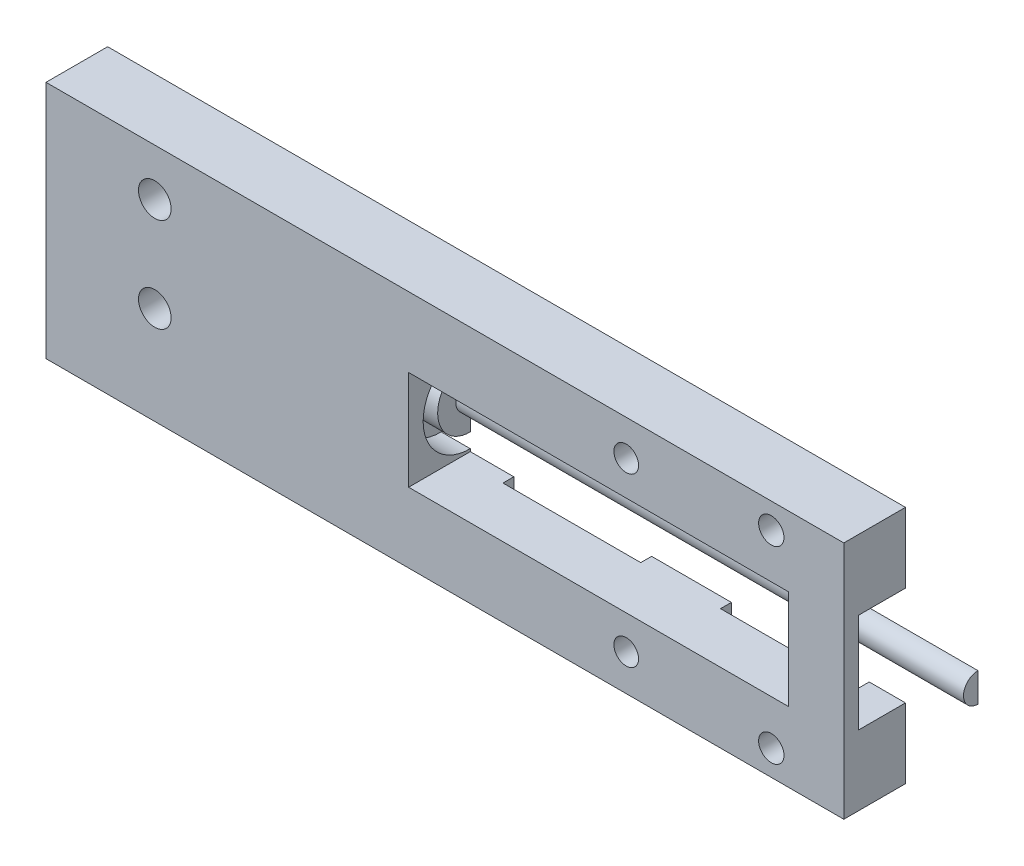
SolidWorks part; units mm, degrees
ref_plane "Plano frontal" through (0, 0, 0) normal (0, 0, 1) x (1, 0, 0)
ref_plane "Plano superior" through (0, 0, 0) normal (0, 1, 0) x (1, 0, 0)
ref_plane "Plano direito" through (0, 0, 0) normal (1, 0, 0) x (0, 0, -1)
sketch "Esboço4" plane through (0, 0, 0) normal (0, 0, 1) x (1, 0, 0)
  line L0 (-80, 16.5) -> (30, 16.5)
  line L1 (-80, -16.5) -> (-80, 16.5)
  line L2 (-80, -16.5) -> (30, -16.5)
  line L3 (30, 16.5) -> (30, 6.85)
  line L4 (30, -16.5) -> (30, -6.85)
  line L5 (30, -6.85) -> (-30, -6.85)
  line L6 (30, 6.85) -> (-30, 6.85)
  line L7 (-30, 6.85) -> (-30, -6.85)
extrude "Ressalto-extrusão1" add sketch "Esboço4" along normal blind 8.5
ref_plane "Plano1" through (-30, 6.85, 8.5) normal (0, 1, 0) x (1, 0, 0)
sketch "Esboço5" plane through (-30, 6.85, 8.5) normal (0, 1, 0) x (1, 0, 0)
  line L0 (6, 7) -> (25, 7)
  line L1 (55, 8.5) -> (55, 7)
  line L2 (6, 7) -> (6, 8.5)
  line L3 (6, 8.5) -> (25, 8.5)
  line L4 (0, 8.5) -> (60, 8.5) construction
  line L5 (25, 8.5) -> (25, 7)
  line L6 (36, 8.5) -> (36, 7)
  line L7 (36, 7) -> (55, 7)
  line L8 (36, 8.5) -> (55, 8.5)
ref_plane "Plano2" through (-30, -6.85, 8.5) normal (0, 1, 0) x (1, 0, 0)
sketch "Esboço8" plane through (-30, -6.85, 8.5) normal (0, 1, 0) x (1, 0, 0)
  line L0 (6, 7) -> (25, 7)
  line L1 (6, 7) -> (6, 8.5)
  line L2 (60, 8.5) -> (0, 8.5) construction
  line L3 (6, 8.5) -> (25, 8.5)
  line L4 (25, 8.5) -> (25, 7)
  line L5 (55, 8.5) -> (55, 7)
  line L6 (36, 8.5) -> (36, 7)
  line L7 (55, 7) -> (36, 7)
  line L8 (55, 8.5) -> (36, 8.5)
extrude "Corte-extrusão1" cut sketch "Esboço8" against normal blind 3 contours L0 L4 L3 L1
extrude "Corte-extrusão2" cut sketch "Esboço5" along normal blind 3
ref_plane "Plano4" through (-80, 16.5, 8.5) normal (0, 0, -1) x (-1, 0, 0)
sketch "Esboço9" plane through (-80, 16.5, 8.5) normal (0, 0, -1) x (-1, 0, 0)
  circle A0 centre (-15, -6.5) radius 3
  circle A1 centre (-15, -19.5) radius 3
  circle A2 centre (-42, -19.5) radius 3
  circle A3 centre (-42, -6.5) radius 3
  circle A4 centre (-42, -6.5) radius 1.62
  circle A5 centre (-42, -19.5) radius 1.62
sketch "Esboço11" plane through (0, 0, 8.5) normal (0, 0, 1) x (1, 0, 0)
  circle A0 centre (-65, 10) radius 2.25
  circle A1 centre (-65, 10) radius 3 construction
  circle A2 centre (0, 11.6) radius 1.7
  circle A3 centre (0, -11.5) radius 1.7
  circle A4 centre (0, -11.5) radius 3
  circle A5 centre (0, 11.6) radius 3
  dimension "D1" = 3.4
  dimension "D2" = 3.4
sketch "Esboço12" plane through (-80, 16.5, 8.5) normal (0, 0, -1) x (-1, 0, 0)
  circle A0 centre (-15, -19.5) radius 2.25
  circle A1 centre (-15, -19.5) radius 3 construction
extrude "Corte-extrusão6" cut sketch "Esboço11" against normal through all contours A0
extrude "Corte-extrusão7" cut sketch "Esboço12" along normal through all contours A0
sketch "Esboço14" plane through (-80, 16.5, 8.5) normal (0, 0, -1) x (-1, 0, 0)
  circle A0 centre (-15, -6.5) radius 3
  circle A1 centre (-15, -6.5) radius 2.25 construction
ref_plane "Plano5" through (-30, -6.85, 0) normal (-1, 0, 0) x (0, 0, 1)
sketch "Esboço15" plane through (-30, -6.85, 0) normal (-1, 0, 0) x (0, 0, 1)
  line L0 (0, 0) -> (0, 13.7) construction
  circle A0 centre (0, 6.85) radius 6.5
extrude "Corte-extrusão12" cut sketch "Esboço15" along normal blind 4
ref_plane "Plano6" through (-34, -6.5, 0) normal (1, 0, 0) x (0, 0, -1)
sketch "Esboço16" plane through (-34, -6.5, 0) normal (1, 0, 0) x (0, 0, -1)
  line L2 (0, 2) -> (0, 11)
  arc A5 (0, 2) -> (0, 11) centre (0, 6.5) cw
extrude "Ressalto-extrusão2" add sketch "Esboço16" along normal blind 4
ref_plane "Plano7" through (-80, 16.5, 0) normal (0, 0, -1) x (-1, 0, 0)
sketch "Esboço17" plane through (-80, 16.5, 0) normal (0, 0, -1) x (-1, 0, 0)
  circle A0 centre (-5, -3) radius 1.8
  circle A1 centre (-5, -26) radius 1.8
  circle A3 centre (-52, -26) radius 1.8
  circle A4 centre (-52, -3) radius 1.8
  circle A5 centre (-107, -26) radius 1.7
  circle A6 centre (-107, -3) radius 1.8
  dimension "D1" = 3.4
  dimension "D2" = 3.6
  dimension "D3" = 3.6
  dimension "D4" = 3.6
  dimension "D5" = 3.6
  dimension "D6" = 3.6
extrude "Corte-extrusão13" cut sketch "Esboço17" against normal blind 1.6
extrude "Corte-extrusão14" cut sketch "Esboço8<4>" against normal blind 3
sketch "Esboço8<4>" plane through (-30, -6.85, 8.5) normal (0, 1, 0) x (1, 0, 0) same geometry as "Esboço8"
extrude "Corte-extrusão18" cut sketch "Esboço11<7>" against normal through all contours A3 | A2 region at (0, 11.6, 8.5) region at (0, -11.5, 8.5)
sketch "Esboço11<7>" plane through (0, 0, 8.5) normal (0, 0, 1) x (1, 0, 0) same geometry as "Esboço11"
ref_plane "Plano8" through (-30, -4.5, 0) normal (-1, 0, 0) x (0, 0, 1)
sketch "Esboço18" plane through (-30, -4.5, 0) normal (-1, 0, 0) x (0, 0, 1)
  line L1 (0, 2.5) -> (0, 6.5)
  arc A1 (0, 2.5) -> (0, 6.5) centre (0, 4.5) ccw
extrude "Ressalto-extrusão3" add sketch "Esboço18" against normal blind 70
sketch "Skizze1" plane through (0, -6.85, 0) normal (0, 1, 0) x (1, 0, 0)
  line L1 (30, -8.5) -> (22.4, -8.5)
  line L2 (30, -8.5) -> (30, -6.5)
  line L3 (30, -6.5) -> (22.4, -6.5)
  line L4 (22.4, -8.5) -> (22.4, -6.5)
  line L5 (17.4, 7.5) -> (17.4, 4) construction
  dimension "D1" = 2
  dimension "D2" = 5
extrude "Aufsatz-Linear austragen1" add sketch "Skizze1" along normal blind 15
sketch "Sketch1" plane through (0, 0, 8.5) normal (0, 0, 1) x (1, 0, 0)
  circle A2 centre (20, 13) radius 1.75
  circle A3 centre (20, -13) radius 1.75
  circle A4 centre (20, -13) radius 3
  circle A5 centre (20, 13) radius 3
  dimension "D1" = 3.5
  dimension "D2" = 3.5
extrude "Cut-Extrude1" cut sketch "Sketch1" against normal blind 10 contours A3 | A2
